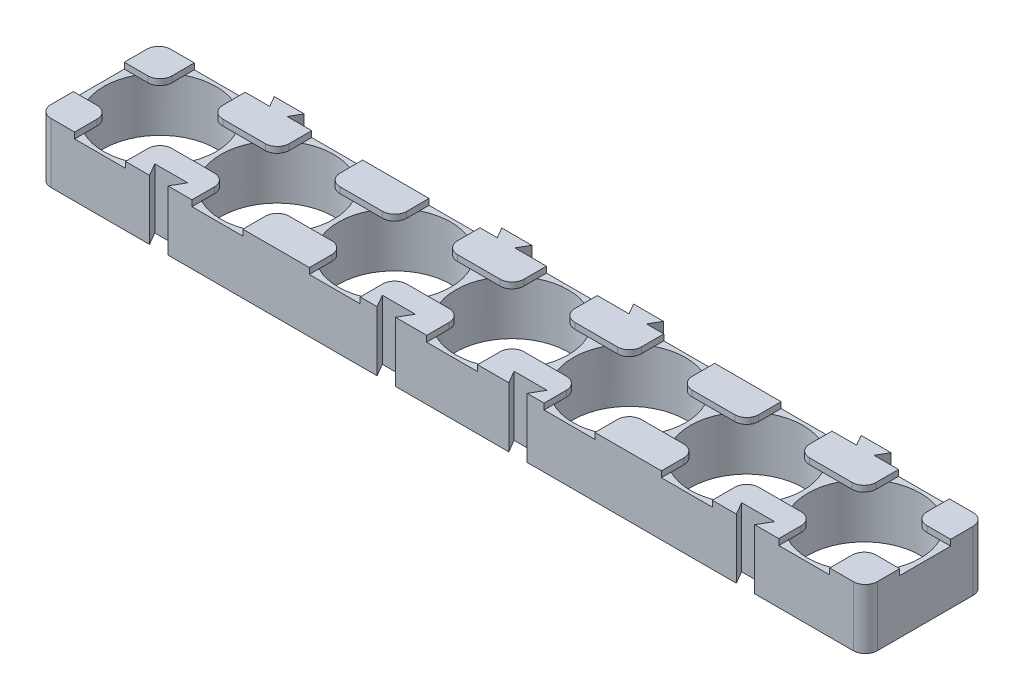
SolidWorks part; units mm, degrees
ref_plane "Front Plane" through (0, 0, 0) normal (0, 0, 1) x (1, 0, 0)
ref_plane "Top Plane" through (0, 0, 0) normal (0, 1, 0) x (1, 0, 0)
ref_plane "Right Plane" through (0, 0, 0) normal (1, 0, 0) x (0, 0, -1)
sketch "Sketch3" plane through (0, 0, 0) normal (0, 1, 0) x (1, 0, 0)
  line L0 (-69, 0) -> (69, 0) construction
  line L1 (-69, -10) -> (69, -10)
  line L2 (-69, -10) -> (-69, 10)
  line L3 (-69, 10) -> (69, 10)
  line L4 (69, -10) -> (69, 10)
  line L5 (-69, -10) -> (69, 10) construction
  line L6 (-69, 10) -> (69, -10) construction
  line L7 (0, -10) -> (0, 10) construction
  line L8 (-49, -15.6732) -> (-49, 15.6732) construction
  line L9 (-30, -10) -> (-30, 10) construction
  line L10 (-50.4608, 10) -> (-51.5, 11.8)
  line L11 (-51.5, 11.8) -> (-46.5, 11.8)
  line L12 (-47.5392, 10) -> (-46.5, 11.8)
  line L13 (-50.4608, 10) -> (-47.5392, 10)
  line L14 (-9.5392, 10) -> (-8.5, 11.8)
  line L15 (-8.5, 11.8) -> (-13.5, 11.8)
  line L16 (-12.4608, 10) -> (-13.5, 11.8)
  line L17 (-9.5392, 10) -> (-12.4608, 10)
  line L18 (9.5392, 10) -> (12.4608, 10)
  line L19 (12.4608, 10) -> (13.5, 11.8)
  line L20 (8.5, 11.8) -> (13.5, 11.8)
  line L21 (9.5392, 10) -> (8.5, 11.8)
  line L22 (50.4608, 10) -> (51.5, 11.8)
  line L23 (51.5, 11.8) -> (46.5, 11.8)
  line L24 (47.5392, 10) -> (46.5, 11.8)
  line L25 (50.4608, 10) -> (47.5392, 10)
  line L26 (-46.25, -7.9) -> (-51.75, -7.9)
  line L27 (-51.75, -7.9) -> (-50.5376, -10)
  line L28 (-46.25, -7.9) -> (-47.4624, -10)
  line L29 (-50.5376, -10) -> (-47.4624, -10)
  line L30 (-8.25, -7.9) -> (-9.4624, -10)
  line L31 (-13.75, -7.9) -> (-8.25, -7.9)
  line L32 (-13.75, -7.9) -> (-12.5376, -10)
  line L33 (-9.4624, -10) -> (-12.5376, -10)
  line L34 (13.75, -7.9) -> (8.25, -7.9)
  line L35 (13.75, -7.9) -> (12.5376, -10)
  line L36 (9.4624, -10) -> (12.5376, -10)
  line L37 (8.25, -7.9) -> (9.4624, -10)
  line L38 (51.75, -7.9) -> (50.5376, -10)
  line L39 (46.25, -7.9) -> (51.75, -7.9)
  line L40 (46.25, -7.9) -> (47.4624, -10)
  line L41 (50.5376, -10) -> (47.4624, -10)
  circle A0 centre (58.8, 0) radius 9.4
  circle A1 centre (39.2, 0) radius 9.4
  circle A2 centre (19.6, 0) radius 9.4
  circle A3 centre (0, 0) radius 9.4
  circle A4 centre (-19.6, 0) radius 9.4
  circle A5 centre (-39.2, 0) radius 9.4
  circle A6 centre (-58.8, 0) radius 9.4
  point P0 (0, 0)
  point P9 (0, 0)
  point P25 (0, 0)
  point P29 (-49, 0)
  point P35 (-30, 0)
  point P37 (-49, 11.8)
  point P53 (-49, -7.9)
  dimension "D1" = 18.8
  dimension "D2" = 20
  dimension "D3" = 10.2
  dimension "D4" = 138
  dimension "D6" = 19.6
  dimension "D7" = 20
  dimension "D8" = 19
  dimension "D9" = 60
  dimension "D10" = 1.8
  dimension "D11" = 5
  dimension "D12" = 60
  dimension "D13" = 5.5
  dimension "D14" = 2.1
  dimension "D5" = 7
extrude "Boss-Extrude1" add sketch "Sketch3" along normal blind 10 contours L40 L39 L38 L1 L4 L3 L2 L27 L26 L28 L32 L31 L30 L37 L34 L35 A6 A5 A4 A3 A2 A1 A0 | L3 L12 L11 L10 | L16 L3 L14 L15 | L21 L3 L19 L20 | L24 L3 L22 L23 region at (-68.8606, 0, 0) region at (-49, 0, -10.9787) region at (-11, 0, -10.9787) region at (11, 0, -10.9787) region at (49, 0, -10.9787)
sketch "Sketch4" plane through (0, 10, 0) normal (0, 1, 0) x (1, 0, 0)
  line L0 (-69, 0) -> (69, 0) construction
  line L1 (-69, 10) -> (69, 10)
  line L2 (-69, 10) -> (-69, -10)
  line L3 (-69, -10) -> (69, -10)
  line L4 (69, 10) -> (69, -10)
  line L5 (58.8, -10) -> (58.8, 10) construction
  line L11 (-69, -4.25) -> (69, -4.25)
  line L12 (-69, -4.25) -> (-69, 4.25)
  line L17 (-69, 4.25) -> (69, 4.25)
  line L18 (69, -4.25) -> (69, 4.25)
  line L19 (-69, -4.25) -> (69, 4.25) construction
  line L20 (-69, 4.25) -> (69, -4.25) construction
  line L21 (54.55, -10) -> (63.05, -10)
  line L22 (54.55, -10) -> (54.55, 10)
  line L23 (54.55, 10) -> (63.05, 10)
  line L24 (63.05, -10) -> (63.05, 10)
  line L25 (54.55, -10) -> (63.05, 10) construction
  line L26 (54.55, 10) -> (63.05, -10) construction
  line L52 (39.2, -10) -> (39.2, 10) construction
  circle A2 centre (58.8, 0) radius 9.4
  circle A3 centre (58.8, 0) radius 9.4 construction
  point P4 (0, 0)
  point P10 (0, 0)
  point P15 (58.8, 0)
  point P16 (0, 0)
  point P53 (39.2, 0)
  circle M27 centre (58.8, 0) radius 9.4
  dimension "D1" = 8.5
  dimension "D2" = 0
  dimension "D4" = 19.6
extrude "Boss-Extrude2" add sketch "Sketch4" against normal blind 1 contours L17 L22 M27 | L22 L11 M27 | L24 L11 M27 | L24 L17 M27 region at (53.0273, 10, -5.7727) region at (64.5727, 10, -5.7727) region at (53.0273, 10, 5.7727) region at (64.5727, 10, 5.7727)
fillet "Fillet2" radius 2 4 edges at (54.55, 9.5, -4.25) (54.55, 9.5, 4.25) (63.05, 9.5, 4.25) (63.05, 9.5, -4.25)
pattern_linear "LPattern1" count 7 spacing 19.6 along (-1, 0, 0) of "Fillet2", "Boss-Extrude2"
fillet "Fillet3" radius 2 4 edges at (69, 5, 10) (69, 5, -10) (-69, 5, 10) (-69, 5, -10)
extrude "Cut-Extrude2" cut sketch "Sketch4<5>" against normal blind 1 contours L17 L18 L11 L12
sketch "Sketch4<5>" plane through (0, 10, 0) normal (0, 1, 0) x (1, 0, 0) same geometry as "Sketch4"
extrude "Cut-Extrude3" cut sketch "Sketch4<6>" against normal blind 1 contours L22 L23 L24 L21
sketch "Sketch4<6>" plane through (0, 10, 0) normal (0, 1, 0) x (1, 0, 0) same geometry as "Sketch4"
pattern_linear "LPattern2" count 7 spacing 19.6 along (-1, 0, 0) of "Cut-Extrude3"
